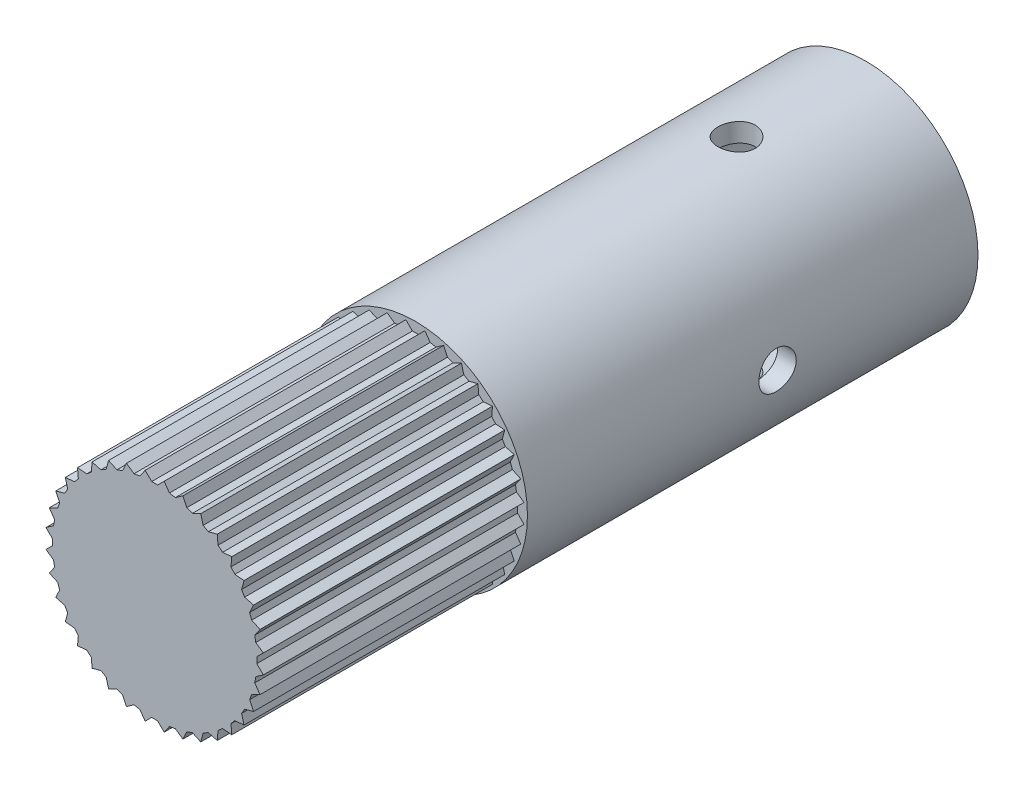
SolidWorks part; units mm, degrees
material "AISI 4130 Steel, annealed at 865C"
ref_plane "X-Y Datum" through (0, 0, 0) normal (0, 0, 1) x (1, 0, 0)
ref_plane "X-Z Datum" through (0, 0, 0) normal (0, 1, 0) x (1, 0, 0)
ref_plane "Y-Z Datum" through (0, 0, 0) normal (1, 0, 0) x (0, 0, -1)
sketch "Sketch9" plane through (0, 0, 0) normal (0, 1, 0) x (1, 0, 0)
  line L0 (16.002, 0) -> (0, 0)
  line L1 (0, 0) -> (0, -389.0916)
  line L2 (0, -389.0916) -> (-72.2493, -524.9728)
  dimension "D1" = 153.895
  dimension "D2" = 28
  dimension "D3" = 389.0916
  dimension "D5" = 16.002
sketch "Sketch5" plane through (0, 0, 0) normal (0, 1, 0) x (1, 0, 0)
  line L0 (7.9375, -82.6177) -> (7.9375, -22.1615)
  line L1 (7.9375, -22.1615) -> (9.525, -22.1615)
  line L2 (9.525, -22.1615) -> (9.525, -82.6177)
  line L3 (9.525, -82.6177) -> (7.9375, -82.6177)
  line L5 (16.002, 0) -> (0, 0) construction
  line L6 (0, 0) -> (0, -389.0916) construction
  line L7 (0, -389.0916) -> (9.525, -389.0916) construction
  line L8 (12.5602, -58.6916) -> (0, -58.6916) construction
  dimension "D1" = 1.5875
  dimension "D2" = 22.1615
  dimension "D3" = 7.9375
  dimension "D4" = 330.4
  dimension "D5" = 306.4739
revolve "Revolve2" add sketch "Sketch5" angle 360 about L1
sketch "Sketch6" plane through (0, 0, 0) normal (0, 1, 0) x (1, 0, 0)
  circle A0 centre (0, -33.1635) radius 1.5875 construction
  circle A1 centre (0, -33.1635) radius 1.5875
sketch "Sketch7" plane through (0, 0, 0) normal (1, 0, 0) x (0, 0, -1)
  circle A2 centre (-39.196, 0) radius 1.5875
  circle A4 centre (-39.196, 0) radius 1.5875 construction
extrude "Cut-Extrude5" cut sketch "Sketch7" against normal through all both and the other way through all
extrude "Cut-Extrude6" cut sketch "Sketch6" against normal through all both and the other way through all
sketch "Sketch8" plane through (0, 0, 0) normal (0, 0, 1) x (1, 0, 0)
  line L0 (9.2357, -0.808) -> (8.6817, -0.254)
  line L1 (8.6817, -0.254) -> (8.6817, 0.254)
  line L2 (8.6817, 0.254) -> (9.2357, 0.808)
  line L3 (8.6817, 0) -> (0, 0) construction
  line L4 (8.9551, -2.3995) -> (8.5057, -1.7577)
  line L5 (8.5057, -1.7577) -> (8.5939, -1.2574)
  line L6 (8.5939, -1.2574) -> (9.2357, -0.808)
  line L7 (8.4024, -3.9181) -> (8.0713, -3.208)
  line L8 (8.0713, -3.208) -> (8.245, -2.7306)
  line L9 (8.245, -2.7306) -> (8.9551, -2.3995)
  line L10 (7.5944, -5.3176) -> (7.3916, -4.5608)
  line L11 (7.3916, -4.5608) -> (7.6456, -4.1209)
  line L12 (7.6456, -4.1209) -> (8.4024, -3.9181)
  line L13 (6.5556, -6.5556) -> (6.4873, -5.7751)
  line L14 (6.4873, -5.7751) -> (6.8138, -5.3859)
  line L15 (6.8138, -5.3859) -> (7.5944, -5.3176)
  line L16 (5.3176, -7.5944) -> (5.3859, -6.8138)
  line L17 (5.3859, -6.8138) -> (5.7751, -6.4873)
  line L18 (5.7751, -6.4873) -> (6.5556, -6.5556)
  line L19 (3.9181, -8.4024) -> (4.1209, -7.6456)
  line L20 (4.1209, -7.6456) -> (4.5608, -7.3916)
  line L21 (4.5608, -7.3916) -> (5.3176, -7.5944)
  line L22 (2.3995, -8.9551) -> (2.7306, -8.245)
  line L23 (2.7306, -8.245) -> (3.208, -8.0713)
  line L24 (3.208, -8.0713) -> (3.9181, -8.4024)
  line L25 (0.808, -9.2357) -> (1.2574, -8.5939)
  line L26 (1.2574, -8.5939) -> (1.7577, -8.5057)
  line L27 (1.7577, -8.5057) -> (2.3995, -8.9551)
  line L28 (-0.808, -9.2357) -> (-0.254, -8.6817)
  line L29 (-0.254, -8.6817) -> (0.254, -8.6817)
  line L30 (0.254, -8.6817) -> (0.808, -9.2357)
  line L31 (-2.3995, -8.9551) -> (-1.7577, -8.5057)
  line L32 (-1.7577, -8.5057) -> (-1.2574, -8.5939)
  line L33 (-1.2574, -8.5939) -> (-0.808, -9.2357)
  line L34 (-3.9181, -8.4024) -> (-3.208, -8.0713)
  line L35 (-3.208, -8.0713) -> (-2.7306, -8.245)
  line L36 (-2.7306, -8.245) -> (-2.3995, -8.9551)
  line L37 (-5.3176, -7.5944) -> (-4.5608, -7.3916)
  line L38 (-4.5608, -7.3916) -> (-4.1209, -7.6456)
  line L39 (-4.1209, -7.6456) -> (-3.9181, -8.4024)
  line L40 (-6.5556, -6.5556) -> (-5.7751, -6.4873)
  line L41 (-5.7751, -6.4873) -> (-5.3859, -6.8138)
  line L42 (-5.3859, -6.8138) -> (-5.3176, -7.5944)
  line L43 (-7.5944, -5.3176) -> (-6.8138, -5.3859)
  line L44 (-6.8138, -5.3859) -> (-6.4873, -5.7751)
  line L45 (-6.4873, -5.7751) -> (-6.5556, -6.5556)
  line L46 (-8.4024, -3.9181) -> (-7.6456, -4.1209)
  line L47 (-7.6456, -4.1209) -> (-7.3916, -4.5608)
  line L48 (-7.3916, -4.5608) -> (-7.5944, -5.3176)
  line L49 (-8.9551, -2.3995) -> (-8.245, -2.7306)
  line L50 (-8.245, -2.7306) -> (-8.0713, -3.208)
  line L51 (-8.0713, -3.208) -> (-8.4024, -3.9181)
  line L52 (-9.2357, -0.808) -> (-8.5939, -1.2574)
  line L53 (-8.5939, -1.2574) -> (-8.5057, -1.7577)
  line L54 (-8.5057, -1.7577) -> (-8.9551, -2.3995)
  line L55 (-9.2357, 0.808) -> (-8.6817, 0.254)
  line L56 (-8.6817, 0.254) -> (-8.6817, -0.254)
  line L57 (-8.6817, -0.254) -> (-9.2357, -0.808)
  line L58 (-8.9551, 2.3995) -> (-8.5057, 1.7577)
  line L59 (-8.5057, 1.7577) -> (-8.5939, 1.2574)
  line L60 (-8.5939, 1.2574) -> (-9.2357, 0.808)
  line L61 (-8.4024, 3.9181) -> (-8.0713, 3.208)
  line L62 (-8.0713, 3.208) -> (-8.245, 2.7306)
  line L63 (-8.245, 2.7306) -> (-8.9551, 2.3995)
  line L64 (-7.5944, 5.3176) -> (-7.3916, 4.5608)
  line L65 (-7.3916, 4.5608) -> (-7.6456, 4.1209)
  line L66 (-7.6456, 4.1209) -> (-8.4024, 3.9181)
  line L67 (-6.5556, 6.5556) -> (-6.4873, 5.7751)
  line L68 (-6.4873, 5.7751) -> (-6.8138, 5.3859)
  line L69 (-6.8138, 5.3859) -> (-7.5944, 5.3176)
  line L70 (-5.3176, 7.5944) -> (-5.3859, 6.8138)
  line L71 (-5.3859, 6.8138) -> (-5.7751, 6.4873)
  line L72 (-5.7751, 6.4873) -> (-6.5556, 6.5556)
  line L73 (-3.9181, 8.4024) -> (-4.1209, 7.6456)
  line L74 (-4.1209, 7.6456) -> (-4.5608, 7.3916)
  line L75 (-4.5608, 7.3916) -> (-5.3176, 7.5944)
  line L76 (-2.3995, 8.9551) -> (-2.7306, 8.245)
  line L77 (-2.7306, 8.245) -> (-3.208, 8.0713)
  line L78 (-3.208, 8.0713) -> (-3.9181, 8.4024)
  line L79 (-0.808, 9.2357) -> (-1.2574, 8.5939)
  line L80 (-1.2574, 8.5939) -> (-1.7577, 8.5057)
  line L81 (-1.7577, 8.5057) -> (-2.3995, 8.9551)
  line L82 (0.808, 9.2357) -> (0.254, 8.6817)
  line L83 (0.254, 8.6817) -> (-0.254, 8.6817)
  line L84 (-0.254, 8.6817) -> (-0.808, 9.2357)
  line L85 (2.3995, 8.9551) -> (1.7577, 8.5057)
  line L86 (1.7577, 8.5057) -> (1.2574, 8.5939)
  line L87 (1.2574, 8.5939) -> (0.808, 9.2357)
  line L88 (3.9181, 8.4024) -> (3.208, 8.0713)
  line L89 (3.208, 8.0713) -> (2.7306, 8.245)
  line L90 (2.7306, 8.245) -> (2.3995, 8.9551)
  line L91 (5.3176, 7.5944) -> (4.5608, 7.3916)
  line L92 (4.5608, 7.3916) -> (4.1209, 7.6456)
  line L93 (4.1209, 7.6456) -> (3.9181, 8.4024)
  line L94 (6.5556, 6.5556) -> (5.7751, 6.4873)
  line L95 (5.7751, 6.4873) -> (5.3859, 6.8138)
  line L96 (5.3859, 6.8138) -> (5.3176, 7.5944)
  line L97 (7.5944, 5.3176) -> (6.8138, 5.3859)
  line L98 (6.8138, 5.3859) -> (6.4873, 5.7751)
  line L99 (6.4873, 5.7751) -> (6.5556, 6.5556)
  line L100 (8.4024, 3.9181) -> (7.6456, 4.1209)
  line L101 (7.6456, 4.1209) -> (7.3916, 4.5608)
  line L102 (7.3916, 4.5608) -> (7.5944, 5.3176)
  line L103 (8.9551, 2.3995) -> (8.245, 2.7306)
  line L104 (8.245, 2.7306) -> (8.0713, 3.208)
  line L105 (8.0713, 3.208) -> (8.4024, 3.9181)
  line L106 (9.2357, 0.808) -> (8.5939, 1.2574)
  line L107 (8.5939, 1.2574) -> (8.5057, 1.7577)
  line L108 (8.5057, 1.7577) -> (8.9551, 2.3995)
  circle A0 centre (0, 0) radius 12.7
  circle A1 centre (0, 0) radius 9.271 construction
  circle A2 centre (0, 0) radius 8.6854 construction
  point P153 (0, 0)
  dimension "D1" = 25.4
  dimension "D4" = 18.542
  dimension "D6" = 17.3708
  dimension "D2" = 0.508
  dimension "D3" = 135
  dimension "D5" = 36
ref_plane "Plane1" through (0, 0, 47.5615) normal (0, 0, -1) x (-1, 0, 0)
sketch "Sketch10" plane through (0, 0, 47.5615) normal (0, 0, -1) x (-1, 0, 0)
  circle A0 centre (0, 0) radius 7.9375
  dimension "D1" = 15.875
extrude "Boss-Extrude1" add sketch "Sketch10" against normal up to surface (35.0562 mm away) up to face at (-9.525, 0, 82.6177)
sketch "Sketch11" plane through (0, 0, 22.1615) normal (0, 0, -1) x (-1, 0, 0)
  line L0 (0, 9.525) -> (13.3548, 9.525) construction
  line L1 (0, 9.525) -> (0, 15.4312) construction
  line L2 (-9.525, 0) -> (-9.525, 9.1744) construction
  line L3 (-9.525, 0) -> (-16.674, 0) construction
  circle A0 centre (0, 0) radius 9.525 construction
  point P0 (0, 9.525)
  point P1 (-9.525, 0)
extrude "Cut-Extrude7" cut sketch "Sketch8" along normal blind 25.4 from offset 60.4571
